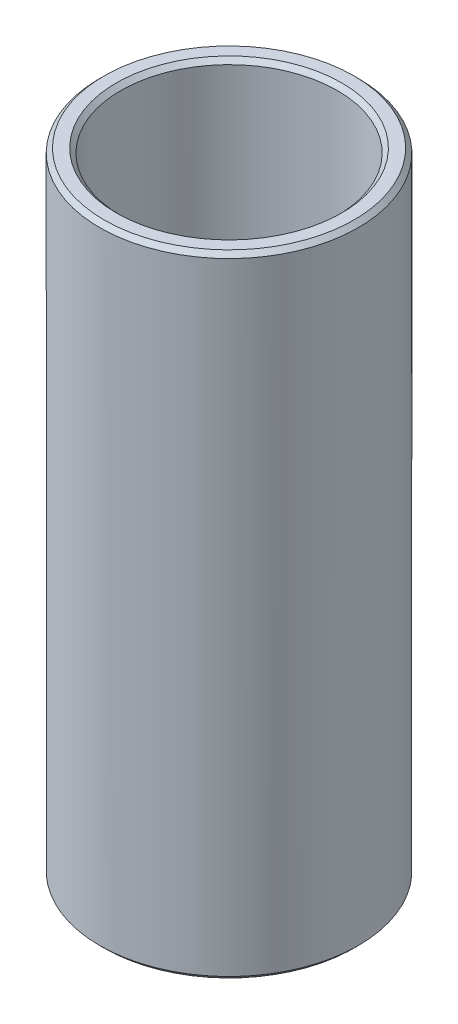
SolidWorks part; units mm, degrees
ref_plane "Front Plane" through (0, 0, 0) normal (0, 0, 1) x (1, 0, 0)
ref_plane "Top Plane" through (0, 0, 0) normal (0, 1, 0) x (1, 0, 0)
ref_plane "Right Plane" through (0, 0, 0) normal (1, 0, 0) x (0, 0, -1)
sketch "Sketch1" plane through (0, 0, 0) normal (0, 1, 0) x (1, 0, 0)
  circle A0 centre (0, 0) radius 47.5
  dimension "SLEEVE_OD" = 95
extrude "Boss-Extrude1" add sketch "Sketch1" along normal blind 231.6681
sketch "Sketch2" plane through (0, 0, 0) normal (0, 1, 0) x (1, 0, 0)
  circle A0 centre (0, 0) radius 39.7825
  dimension "BORE_D" = 79.5651
extrude "Cut-Extrude1" cut sketch "Sketch2" along normal through all
chamfer "Chamfer1" distance 1.6243 angle 45 4 edges at (0, 231.6681, 39.7825) (0, 0, 39.7825) (0, 0, 47.5) (0, 231.6681, 47.5)
